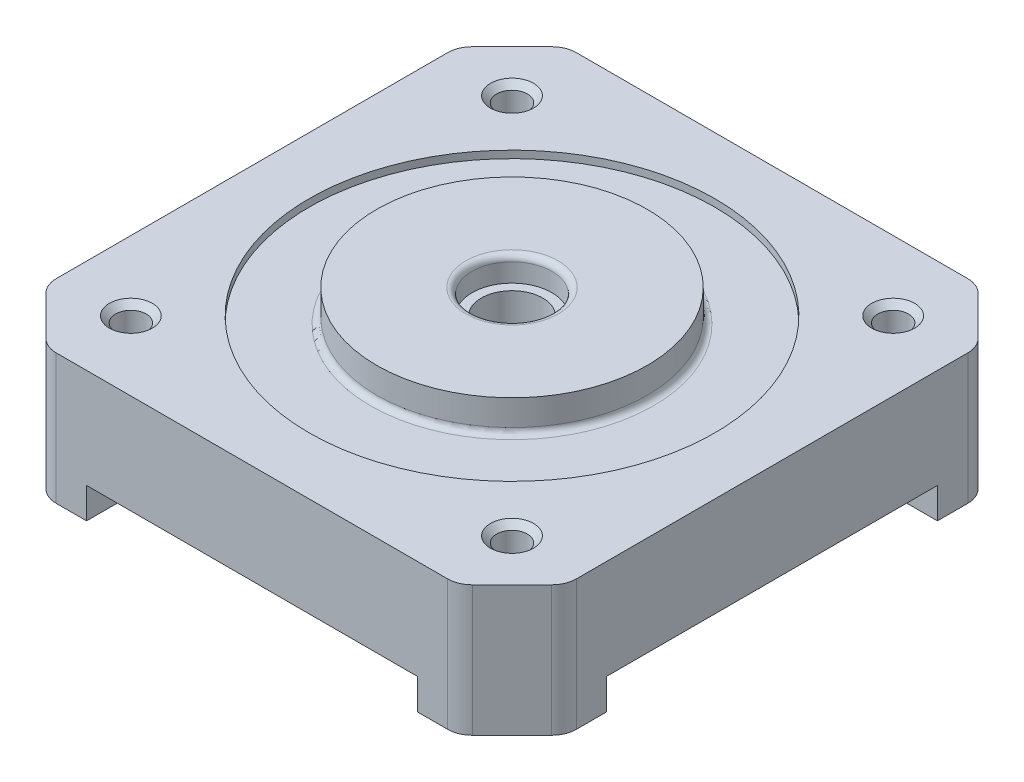
SolidWorks part; units mm, degrees
material "Alumina"
ref_plane "Front Plane" through (0, 0, 0) normal (0, 0, 1) x (1, 0, 0)
ref_plane "Top Plane" through (0, 0, 0) normal (0, 1, 0) x (1, 0, 0)
ref_plane "Right Plane" through (0, 0, 0) normal (1, 0, 0) x (0, 0, -1)
sketch "Sketch1" plane through (0, 0, 0) normal (0, 1, 0) x (1, 0, 0)
  line L0 (-21.15, 16.7509) -> (-16.7509, 21.15)
  line L1 (-16.7509, -21.15) -> (16.7509, -21.15)
  line L2 (-21.15, -16.7509) -> (-21.15, 16.7509)
  line L3 (-16.7509, 21.15) -> (16.7509, 21.15)
  line L4 (21.15, -16.7509) -> (21.15, 16.7509)
  line L7 (16.7509, 21.15) -> (21.15, 16.7509)
  line L8 (16.7509, -21.15) -> (21.15, -16.7509)
  line L9 (-21.15, -16.7509) -> (-16.7509, -21.15)
  point P0 (0, 0)
  dimension "D1" = 42.3
  dimension "D2" = 42.3
  dimension "D3" = 53.6
  dimension "D4" = 45
  dimension "D5" = 45
  dimension "D7" = 53.6
extrude "Boss-Extrude1" add sketch "Sketch1" along normal blind 10.6
sketch "Sketch2" plane through (0, 10.6, 0) normal (0, 1, 0) x (1, 0, 0)
  circle A0 centre (0, 0) radius 16.5
  dimension "D1" = 33
extrude "Cut-Extrude1" cut sketch "Sketch2" against normal blind 0.6
sketch "Sketch3" plane through (0, 10, 0) normal (0, 1, 0) x (1, 0, 0)
  circle A0 centre (0, 0) radius 11
  dimension "D1" = 22
extrude "Boss-Extrude2" add sketch "Sketch3" along normal blind 2.6
sketch "Sketch4" plane through (0, 12.6, 0) normal (0, 1, 0) x (1, 0, 0)
  circle A0 centre (0, 0) radius 3.25
  dimension "D1" = 6.5
extrude "Cut-Extrude2" cut sketch "Sketch4" against normal blind 2
sketch "Sketch5" plane through (0, 10.6, 0) normal (0, 1, 0) x (1, 0, 0)
  circle A0 centre (0, 0) radius 2.5
  dimension "D1" = 5
extrude "Cut-Extrude3" cut sketch "Sketch5" against normal through all
fillet "Fillet1" radius 0.5 1 edges at (0, 12.6, 3.25)
fillet "Fillet2" radius 0.5 1 edges at (0, 10, 11) type face fillet first side face at (0, 12.6, 11) second side face at (0, 10, 16.5)
hole_wizard "M3x0.5 Tapped Hole1" positions "Sketch9" profile "Sketch8" tap size "M3x0.5" standard "ANSI Metric"
sketch "Sketch9" plane through (0, 10.6, 0) normal (0, 1, 0) x (1, 0, 0)
  point P0 (-15.5, 15.5)
  point P2 (15.5, 15.5)
  point P4 (15.5, -15.5)
  point P6 (-15.5, -15.5)
  dimension "D1" = 31
  dimension "D2" = 31
  dimension "D3" = 31
  dimension "D4" = 31
  dimension "D5" = 5.65
  dimension "D6" = 5.65
  dimension "D7" = 5.65
  dimension "D8" = 5.65
sketch "Sketch8" plane through (-15.5, 10.6, -15.5) normal (1, 0, 0) x (0, 0, 1)
  line L0 (0, 0) -> (0, 10.7511)
  line L1 (0, 10.7511) -> (1.25, 10)
  line L2 (1.25, 10) -> (1.25, 0.5)
  line L3 (1.25, 0.5) -> (1.75, 0)
  line L5 (1.75, 0) -> (0, 0)
  line L6 (-1.25, 0.5) -> (-1.75, 0) construction
  line L10 (0, 10.7511) -> (-1.25, 10) construction
  line L11 (0, -6.35) -> (0, 107.95) construction
  dimension "Tap Drill Dia." = 2.5
  dimension "Tap Drill Depth" = 10
  dimension "Near C'Sink Dia." = 3.5
  dimension "Near C'Sink Angle" = 90
  dimension "Drill Angle" = 118
sketch "Sketch10" plane through (0, 0, 21.15) normal (0, 0, 1) x (1, 0, 0)
  line L0 (-13.4509, 0) -> (-13.4509, 2.5)
  line L1 (-16.7509, 0) -> (16.7509, 0) construction
  line L2 (-13.4509, 2.5) -> (13.4509, 2.5)
  line L3 (13.4509, 2.5) -> (13.4509, 0)
  line L4 (-16.7509, 10.6) -> (-16.7509, 0) construction
  line L5 (16.7509, 10.6) -> (16.7509, 0) construction
  line L6 (-13.4509, 0) -> (13.4509, 0)
  dimension "D1" = 3.3
  dimension "D2" = 3.3
  dimension "D3" = 2.5
extrude "Cut-Extrude4" cut sketch "Sketch10" against normal through all
sketch "Sketch11" plane through (-21.15, 0, 0) normal (-1, 0, 0) x (0, 0, 1)
  line L0 (-13.4509, 0) -> (-13.4509, 2.5)
  line L1 (-16.7509, 0) -> (16.7509, 0) construction
  line L2 (-13.4509, 2.5) -> (13.4509, 2.5)
  line L3 (13.4509, 2.5) -> (13.4509, 0)
  line L4 (13.4509, 0) -> (-13.4509, 0)
  line L5 (-16.7509, 10.6) -> (-16.7509, 0) construction
  line L6 (16.7509, 10.6) -> (16.7509, 0) construction
  dimension "D1" = 2.5
  dimension "D2" = 3.3
  dimension "D3" = 3.3
extrude "Cut-Extrude5" cut sketch "Sketch11" against normal through all
fillet "Fillet3" radius 2 8 edges at (-21.15, 5.3, 16.7509) (16.7509, 5.3, -21.15) (21.15, 5.3, -16.7509) (21.15, 5.3, 16.7509) (16.7509, 5.3, 21.15) (-16.7509, 5.3, 21.15) (-16.7509, 5.3, -21.15) (-21.15, 5.3, -16.7509)
